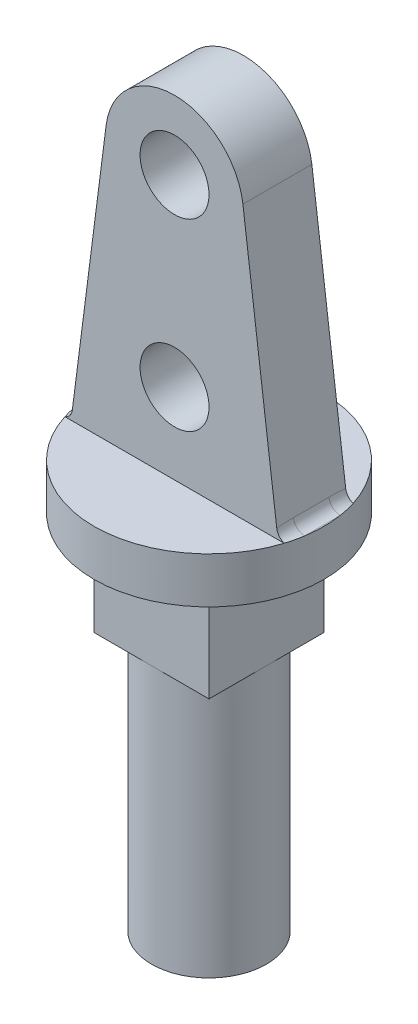
SolidWorks part; units mm, degrees
material "Stainless Steel (ferritic)"
ref_plane "Front Plane" through (0, 0, 0) normal (0, 0, 1) x (1, 0, 0)
ref_plane "Top Plane" through (0, 0, 0) normal (0, 1, 0) x (1, 0, 0)
ref_plane "Right Plane" through (0, 0, 0) normal (1, 0, 0) x (0, 0, -1)
sketch "Sketch1" plane through (0, 0, 0) normal (0, 1, 0) x (1, 0, 0)
  circle A0 centre (0, 0) radius 20
  dimension "D1" = 40
extrude "Boss-Extrude4" add sketch "Sketch1" against normal blind 8 contours A0
sketch "Sketch5" plane through (0, -8, 0) normal (0, -1, 0) x (1, 0, 0)
  line L1 (-10, -10) -> (10, -10)
  line L2 (-10, -10) -> (-10, 10)
  line L3 (-10, 10) -> (10, 10)
  line L4 (10, -10) -> (10, 10)
  line L5 (-10, -10) -> (10, 10) construction
  line L6 (-10, 10) -> (10, -10) construction
  point P0 (0, 0)
  dimension "D1" = 20
  dimension "D2" = 20
extrude "Boss-Extrude5" add sketch "Sketch5" along normal blind 18
sketch "Sketch6" plane through (0, -26, 0) normal (0, -1, 0) x (1, 0, 0)
  circle A0 centre (0, 0) radius 10
  dimension "D1" = 20
extrude "Boss-Extrude6" add sketch "Sketch6" along normal blind 45 contours A0
sketch "Sketch7" plane through (0, 0, 0) normal (0, 0, 1) x (1, 0, 0)
  line L0 (-18, 0) -> (-11.9024, 47.527)
  line L1 (20, 0) -> (-20, 0) construction
  line L2 (0, 60.4869) -> (0, 8) construction
  line L3 (18, 0) -> (11.9024, 47.527)
  line L4 (-18, 0) -> (18, 0)
  circle A0 centre (0, 14) radius 6
  circle A1 centre (0, 46) radius 6
  arc A2 (11.9024, 47.527) -> (-11.9024, 47.527) centre (0, 46) ccw
  dimension "D1" = 12
  dimension "D2" = 12
  dimension "D5" = 24
  dimension "D3" = 32
  dimension "D4" = 14
  dimension "D6" = 2
extrude "Boss-Extrude7" add sketch "Sketch7" along normal mid plane 12
fillet "Fillet1" radius 2 2 edges at (-18, 0, 0) (18, 0, 0)
